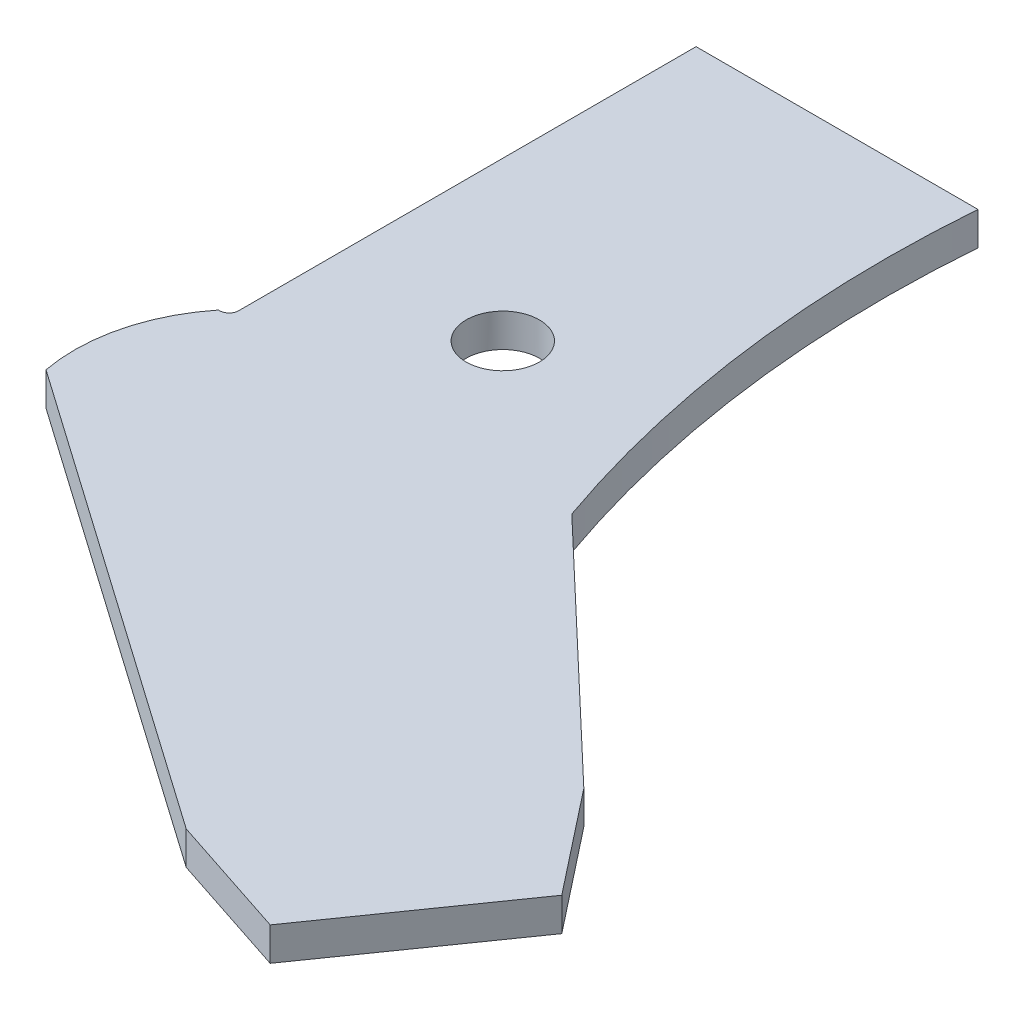
SolidWorks part; units mm, degrees
ref_plane "Front Plane" through (0, 0, 0) normal (0, 0, 1) x (1, 0, 0)
ref_plane "Top Plane" through (0, 0, 0) normal (0, 1, 0) x (1, 0, 0)
ref_plane "Right Plane" through (0, 0, 0) normal (1, 0, 0) x (0, 0, -1)
sketch "Sketch1" plane through (0, 0, 0) normal (0, 1, 0) x (1, 0, 0)
  line L0 (47.0297, 0) -> (-47.0297, 0)
  line L1 (-47.0297, -28.9719) -> (45.8391, -28.9719) construction
  line L2 (-47.0297, 0) -> (-47.0297, -152.5984)
  line L3 (-47.0297, -155.7734) -> (-50.6016, -155.7734) construction
  line L4 (-47.0297, -155.7734) -> (-47.0297, -201.8109) construction
  line L5 (-47.0297, -201.8109) -> (-62.1109, -201.8109) construction
  line L6 (-47.0297, -180.7766) -> (-62.1109, -180.7766) construction
  line L7 (-47.0297, -155.7734) -> (67.2703, -155.7734) construction
  line L8 (5.7547, -125.2141) -> (5.7547, -155.7734) construction
  line L9 (-50.6016, -155.7734) -> (-50.2047, -155.7734)
  line L10 (-62.1109, -201.8109) -> (93.9375, -311.0772)
  line L11 (93.9375, -311.0772) -> (135.6827, -324.8037)
  line L12 (135.6827, -324.8037) -> (175.747, -267.5859)
  line L13 (175.747, -267.5859) -> (148.5707, -233.053)
  line L14 (135.6827, -324.8037) -> (128.3982, -335.2069) construction
  line L15 (128.3982, -335.2069) -> (93.9375, -311.0772) construction
  line L16 (175.747, -267.5859) -> (183.0314, -257.1827) construction
  line L17 (148.5707, -233.053) -> (183.0314, -257.1827) construction
  line L18 (67.2703, -155.7734) -> (148.5707, -233.053)
  arc A0 (-62.1109, -201.8109) -> (-50.6016, -155.7734) centre (-6.35, -191.2937) cw
  circle A1 centre (5.7547, -117.2766) radius 7.9375
  arc A2 (47.0297, 0) -> (67.2703, -155.7734) centre (425.2702, -30.0545) ccw
  arc A3 (-47.0297, -152.5984) -> (-50.2047, -155.7734) centre (-50.2047, -152.5984) cw
  point P4 (0, 0)
  dimension "D11" = 15.875
  dimension "D14" = 3.175
  dimension "D1" = 94.0594
  dimension "D2" = 92.8688
  dimension "D3" = 28.9719
  dimension "D4" = 155.7734
  dimension "D5" = 25.0031
  dimension "D6" = 46.0375
  dimension "D7" = 15.0812
  dimension "D8" = 3.5719
  dimension "D9" = 15.0812
  dimension "D10" = 114.3
  dimension "D12" = 30.5594
  dimension "D13" = 52.7844
  dimension "D15" = 35
  dimension "D16" = 190.5
  dimension "D17" = 69.85
  dimension "D18" = 90
  dimension "D19" = 180
  dimension "D20" = 180
  dimension "D21" = 42.0687
  dimension "D22" = 12.7
  dimension "D23" = 42.0688
  dimension "D24" = 12.7
  dimension "D25" = 90
extrude "Boss-Extrude1" add sketch "Sketch1" along normal blind 11.1125
sketch "Sketch2" plane through (0, 11.1125, 0) normal (0, 1, 0) x (1, 0, 0)
  circle A0 centre (5.7547, -117.2766) radius 12.2039
  dimension "D1" = 24.4078
extrude "Cut-Extrude1" cut sketch "Sketch2" against normal up to surface (11.1125 mm away) up to face at (36.2478, 0, 178.0641)
